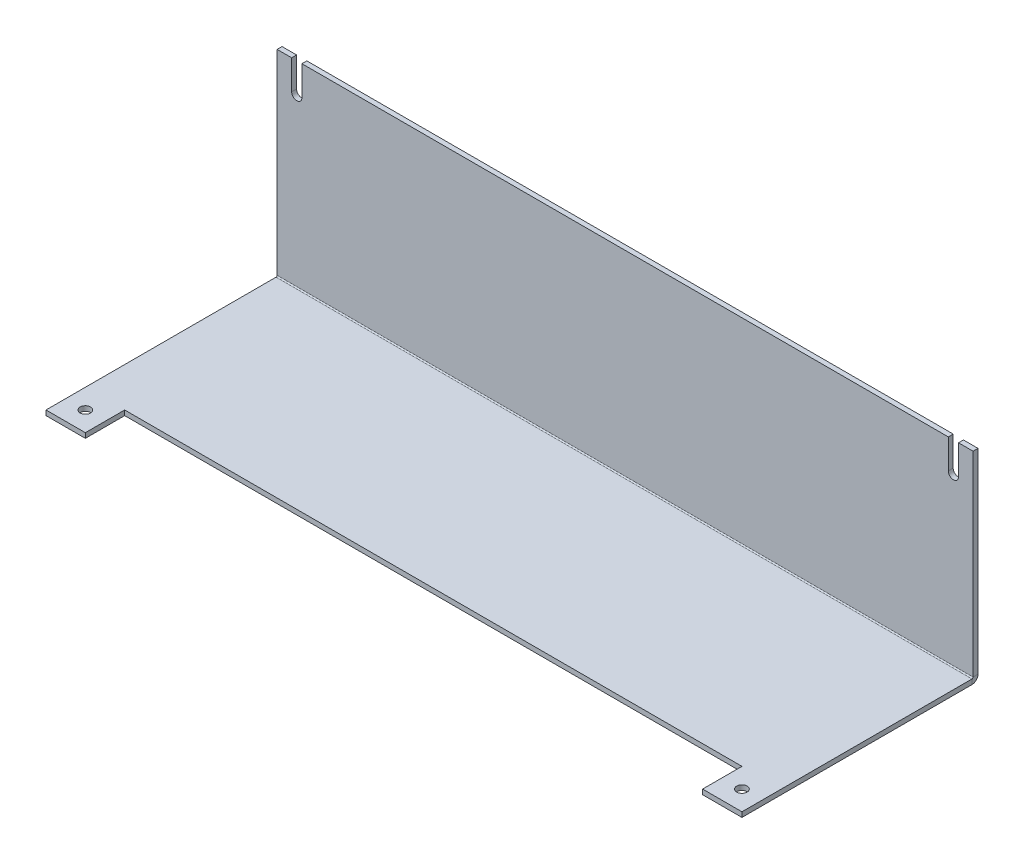
SolidWorks part; units mm, degrees
note: The reader was unsure of these and kept them because the rebuilt part matched: thickness of "Base-Flange1", "Edge-Flange1", "Sheet-Metal(1)", "Sheet-Metal(2)", "Sheet-Metal(3)", "Sheet-Metal(4)", "Sheet-Metal(5)"; flange length of "Edge-Flange1".
ref_plane "Front Plane" through (0, 0, 0) normal (0, 0, 1) x (1, 0, 0)
ref_plane "Top Plane" through (0, 0, 0) normal (0, 1, 0) x (1, 0, 0)
ref_plane "Right Plane" through (0, 0, 0) normal (1, 0, 0) x (0, 0, -1)
sketch "Sketch1" plane through (0, 0, 0) normal (0, 1, 0) x (1, 0, 0)
  line L1 (0, 0) -> (449.326, 0)
  line L2 (0, 0) -> (0, 127)
  line L3 (0, 127) -> (449.326, 127)
  line L4 (449.326, 0) -> (449.326, 127)
  dimension "D1" = 449.326
  dimension "D2" = 127
base flange "Base-Flange1" sketch "Sketch1" thickness 3.175 reverse thickness direction no parameters "D1"=0.7366
edge flange "Edge-Flange1" sketch "Sketch8" flange angle 90 flange length 127 flange position material inside bend radius 0.7366 thickness 3.175 relief rectangular parameters "D6"=10
sketch "Sketch8" plane through (0, 0, -127) normal (0, 0, -1) x (-1, 0, 0)
  line L0 (-449.326, 0) -> (0, 0) construction
  line L1 (-449.326, 0) -> (0, 0)
  line L2 (-449.326, 0) -> (-449.326, 127)
  line L3 (-449.326, 127) -> (0, 127)
  line L4 (0, 127) -> (0, 0)
bend "EdgeBend1" bend radius 0.7366 bend angle 90 parameters "D5"=1
sketch "Sketch9" plane through (0, 0, -127) normal (0, 0, -1) x (-1, 0, 0)
  line L0 (-433.324, 107.95) -> (-433.324, 127)
  line L1 (0, 127) -> (-449.326, 127) construction
  line L2 (-439.928, 107.95) -> (-439.928, 127)
  line L4 (-449.326, 127) -> (-449.326, 0.7366) construction
  line L5 (-439.928, 127) -> (-433.324, 127)
  line L6 (-16.002, 107.95) -> (-16.002, 127)
  line L7 (-16.002, 127) -> (-9.398, 127)
  line L8 (-9.398, 127) -> (-9.398, 107.95)
  line L9 (0, 0.7366) -> (0, 127) construction
  arc A0 (-439.928, 107.95) -> (-433.324, 107.95) centre (-436.626, 107.95) ccw
  arc A1 (-16.002, 107.95) -> (-9.398, 107.95) centre (-12.7, 107.95) ccw
  dimension "D1" = 6.604
  dimension "D4" = 6.604
  dimension "D2" = 19.05
  dimension "D3" = 12.7
  dimension "D5" = 19.05
  dimension "D6" = 12.7
extrude "Cut-Extrude1" cut sketch "Sketch9" against normal through all normal cut yes
sketch "Sketch10" plane through (0, 0, 0) normal (0, 0, 1) x (1, 0, 0)
  line L0 (0, -3.175) -> (449.326, -3.175) construction
  line L1 (449.326, 0) -> (423.926, 0)
  line L2 (449.326, 0) -> (449.326, -3.175)
  line L3 (449.326, -3.175) -> (423.926, -3.175)
  line L4 (423.926, 0) -> (423.926, -3.175)
  line L6 (0, 0) -> (25.4, 0)
  line L7 (0, 0) -> (0, -3.175)
  line L8 (0, -3.175) -> (25.4, -3.175)
  line L9 (25.4, 0) -> (25.4, -3.175)
  dimension "D1" = 25.4
  dimension "D2" = 25.4
extrude "Boss-Extrude1" add sketch "Sketch10" along normal blind 25.4
hole_wizard "1/4 Clearance Hole1" positions "3DSketch1" profile "Sketch11" hole size "1/4" standard "ANSI Inch"
sketch3d "3DSketch1"
  line L0 (449.326, -3.175, 25.4) -> (449.326, -3.175, -123.0884) construction
  line L1 (423.926, -3.175, 25.4) -> (449.326, -3.175, 25.4) construction
  line L2 (25.4, -3.175, 25.4) -> (25.4, -3.175, 0) construction
  line L3 (0, -3.175, 25.4) -> (25.4, -3.175, 25.4) construction
  point P0 (12.7, -3.175, 12.7)
  point P2 (436.626, -3.175, 12.7)
  dimension "D1" = 12.7
  dimension "D2" = 12.7
  dimension "D3" = 12.7
  dimension "D4" = 12.7
sketch "Sketch11" plane through (12.7, -3.175, 12.7) normal (1, 0, 0) x (0, 0, -1)
  line L0 (0, 0) -> (0, 27.4298)
  line L1 (0, 27.4298) -> (3.3782, 25.4)
  line L2 (3.3782, 25.4) -> (3.3782, 0)
  line L5 (3.3782, 0) -> (0, 0)
  line L10 (0, 27.4298) -> (-3.3782, 25.4) construction
  line L11 (0, -6.35) -> (0, 107.95) construction
  dimension "Hole Dia." = 6.7564
  dimension "Hole Depth" = 25.4
  dimension "Drill Angle" = 118
sketch "Bend-Lines1" plane through (0, 0, 0) normal (0, 1, 0) x (1, 0, 0)
sketch "Bounding-Box1" plane through (0, 0, 0) normal (0, 1, 0) x (1, 0, 0)
sheet metal parameters "Sheet-Metal(1)" thickness 3.175 parameters "D1"=0.7366
flat pattern "Flat-Pattern(1)" [suppressed]
sketch "Bend-Lines2" plane through (0, 0, 0) normal (0, 1, 0) x (1, 0, 0)
sketch "Bounding-Box2" [suppressed] plane through (0, 0, 0) normal (0, 1, 0) x (1, 0, 0)
sheet metal parameters "Sheet-Metal(2)" thickness 3.175 parameters "D1"=0.7366
flat pattern "Flat-Pattern(1)" [suppressed]
sketch "Bend-Lines2" plane through (0, 0, 0) normal (0, 1, 0) x (1, 0, 0)
sketch "Bounding-Box2" [suppressed] plane through (0, 0, 0) normal (0, 1, 0) x (1, 0, 0)
bend of the flat pattern "Flatten-<EdgeBend1>1"
sheet metal parameters "Sheet-Metal(3)" thickness 3.175 parameters "D1"=0.7366
flat pattern "Flat-Pattern(1)" [suppressed]
sketch "Bend-Lines2" plane through (0, 0, 0) normal (0, 1, 0) x (1, 0, 0)
sketch "Bounding-Box2" [suppressed] plane through (0, 0, 0) normal (0, 1, 0) x (1, 0, 0)
bend of the flat pattern "Flatten-<EdgeBend1>1"
sheet metal parameters "Sheet-Metal(4)" thickness 3.175 parameters "D1"=0.7366
flat pattern "Flat-Pattern(1)" [suppressed]
sketch "Bend-Lines2" plane through (0, 0, 0) normal (0, 1, 0) x (1, 0, 0)
sketch "Bounding-Box2" [suppressed] plane through (0, 0, 0) normal (0, 1, 0) x (1, 0, 0)
bend of the flat pattern "Flatten-<EdgeBend1>1"
sheet metal parameters "Sheet-Metal(5)" thickness 3.175 parameters "D1"=0.7366
flat pattern "Flat-Pattern(1)" [suppressed]
sketch "Bend-Lines2" plane through (0, 0, 0) normal (0, 1, 0) x (1, 0, 0)
sketch "Bounding-Box2" [suppressed] plane through (0, 0, 0) normal (0, 1, 0) x (1, 0, 0)
bend of the flat pattern "Flatten-<EdgeBend1>1"
